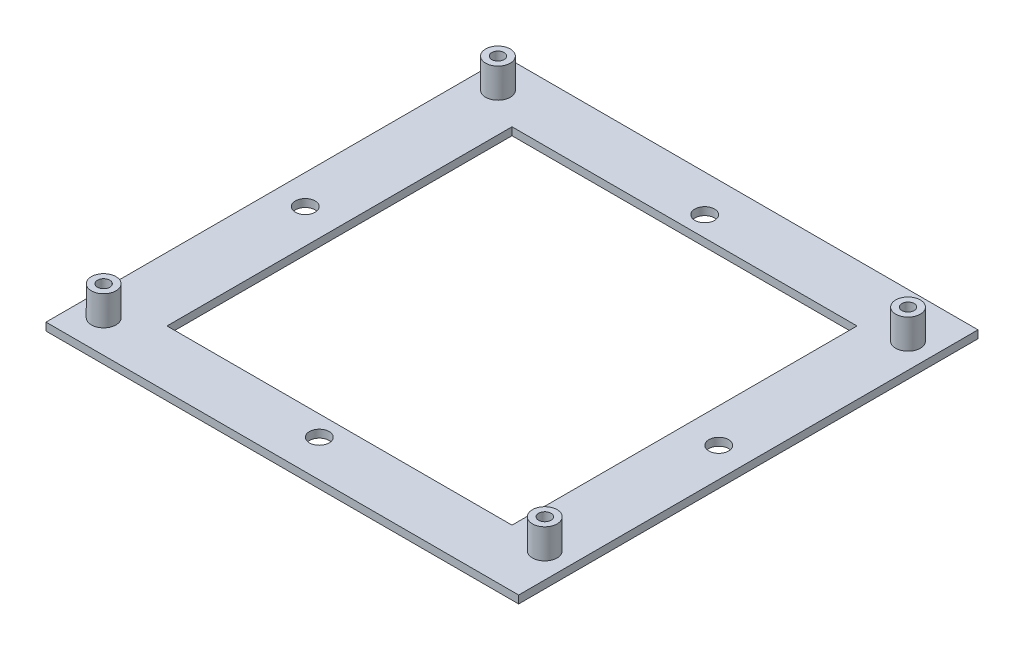
SolidWorks part; units mm, degrees
ref_plane "Front Plane" through (0, 0, 0) normal (0, 0, 1) x (1, 0, 0)
ref_plane "Top Plane" through (0, 0, 0) normal (0, 1, 0) x (1, 0, 0)
ref_plane "Right Plane" through (0, 0, 0) normal (1, 0, 0) x (0, 0, -1)
sketch "Sketch2" plane through (0, 0, 0) normal (0, 1, 0) x (1, 0, 0)
  line L0 (-41.95, 0) -> (41.95, 0) construction
  line L1 (-47.95, -46.6) -> (47.95, -46.6)
  line L2 (-47.95, -46.6) -> (-47.95, 46.6)
  line L3 (-47.95, 46.6) -> (47.95, 46.6)
  line L4 (47.95, -46.6) -> (47.95, 46.6)
  line L5 (-47.95, -46.6) -> (47.95, 46.6) construction
  line L6 (-47.95, 46.6) -> (47.95, -46.6) construction
  line L7 (-35, -35) -> (35, -35)
  line L8 (-35, -35) -> (-35, 35)
  line L9 (-35, 35) -> (35, 35)
  line L10 (35, -35) -> (35, 35)
  line L11 (-35, -35) -> (35, 35) construction
  line L12 (-35, 35) -> (35, -35) construction
  line L13 (0, -39.1) -> (0, 39.1) construction
  circle A0 centre (0, 39.1) radius 2
  circle A1 centre (41.95, 0) radius 2
  circle A2 centre (-41.95, 0) radius 2
  circle A3 centre (0, -39.1) radius 2
  point P0 (0, 0)
  point P6 (0, 0)
  point P11 (42.85, 37.5)
  point P12 (42.85, -36.2)
  point P13 (-42.85, 40)
  point P14 (-42.85, -40)
  point P18 (0, 0)
  point P21 (0, 0)
extrude "Boss-Extrude1" add sketch "Sketch2" along normal blind 1.58
sketch "Sketch3" plane through (0, 1.58, 0) normal (0, 1, 0) x (1, 0, 0)
  circle A0 centre (-42.85, 40) radius 2.5
  circle A1 centre (42.85, 37.5) radius 2.5
  circle A2 centre (-42.85, -40) radius 2.5
  circle A3 centre (42.85, -36.2) radius 2.5
  point P0 (42.85, -36.2)
  point P1 (42.85, 37.5)
  point P2 (-42.85, 40)
  point P3 (-42.85, -40)
extrude "Boss-Extrude2" add sketch "Sketch3" along normal blind 6
hole_wizard "M3x0.5 Tapped Hole1" positions "3DSketch1" profile "Sketch4" tap size "M3x0.5" standard "ANSI Metric"
sketch3d "3DSketch1"
  line L0 (-42.85, 7.58, -40) -> (-42.85, 1.58, -40) construction
  line L1 (-42.85, 7.58, 40) -> (-42.85, 1.58, 40) construction
  line L2 (42.85, 7.58, 36.2) -> (42.85, 1.58, 36.2) construction
  line L3 (42.85, 7.58, -37.5) -> (42.85, 1.58, -37.5) construction
  point P0 (-42.85, 7.58, -40)
  point P4 (-42.85, 7.58, 40)
  point P8 (42.85, 7.58, 36.2)
  point P12 (42.85, 7.58, -37.5)
sketch "Sketch4" plane through (-42.85, 7.58, -40) normal (1, 0, 0) x (0, 0, 1)
  line L0 (0, 0) -> (0, 6.7511)
  line L1 (0, 6.7511) -> (1.25, 6)
  line L2 (1.25, 6) -> (1.25, 0)
  line L5 (1.25, 0) -> (0, 0)
  line L10 (0, 6.7511) -> (-1.25, 6) construction
  line L11 (0, -6.35) -> (0, 107.95) construction
  dimension "Tap Drill Dia." = 2.5
  dimension "Tap Drill Depth" = 6
  dimension "Drill Angle" = 118
cosmetic thread "Hole Thread1" parameters "D1"=6, "D2"=3
cosmetic thread "Hole Thread2" parameters "D1"=6, "D2"=3
cosmetic thread "Hole Thread3" parameters "D1"=6, "D2"=3
cosmetic thread "Hole Thread4" parameters "D1"=6, "D2"=3
